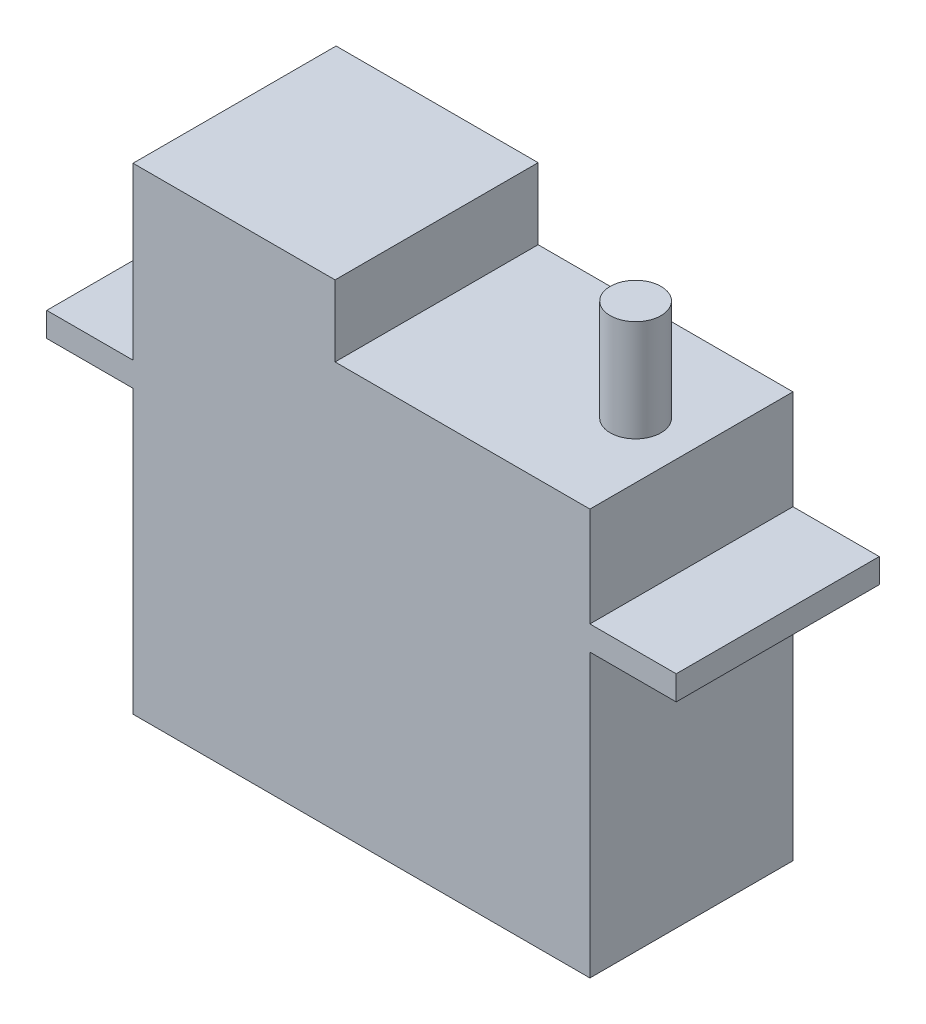
SolidWorks part; units mm, degrees
ref_plane "Plan de face" through (0, 0, 0) normal (0, 0, 1) x (1, 0, 0)
ref_plane "Plan de dessus" through (0, 0, 0) normal (0, 1, 0) x (1, 0, 0)
ref_plane "Plan de droite" through (0, 0, 0) normal (1, 0, 0) x (0, 0, -1)
sketch "Esquisse1" plane through (0, 0, 0) normal (0, 0, 1) x (1, 0, 0)
  line L0 (0, 0) -> (22.5, 0)
  line L1 (22.5, 0) -> (22.5, 15.1) construction
  line L2 (22.5, 15.1) -> (26.75, 15.1)
  line L3 (26.75, 15.1) -> (26.75, 13.9)
  line L4 (26.75, 13.9) -> (22.5, 13.9)
  line L5 (22.5, 13.9) -> (22.5, 20) construction
  line L6 (22.5, 20) -> (9.95, 20)
  line L7 (9.95, 20) -> (9.95, 23.5)
  line L8 (9.95, 23.5) -> (0, 23.5)
  line L9 (0, 23.5) -> (0, 13.9) construction
  line L10 (0, 13.9) -> (-4.25, 13.9)
  line L11 (-4.25, 13.9) -> (-4.25, 15.1)
  line L12 (-4.25, 15.1) -> (0, 15.1)
  line L13 (0, 15.1) -> (0, 0) construction
  line L14 (0, 23.5) -> (0, 15.1)
  line L15 (0, 13.9) -> (0, 0)
  line L16 (22.5, 13.9) -> (22.5, 0)
  line L17 (22.5, 20) -> (22.5, 15.1)
  dimension "D1" = 31
  dimension "D2" = 15.1
  dimension "D3" = 23.5
  dimension "D4" = 20
  dimension "D5" = 1.2
  dimension "D6" = 22.5
  dimension "D7" = 16.8
extrude "Boss.-Extru.1" add sketch "Esquisse1" along normal blind 5 and the other way blind 5 contours L6 L7 L8 L14 L12 L11 L10 L15 L0 L16 L4 L3 L2 L17
sketch "Esquisse3" plane through (0, 20, 0) normal (0, 1, 0) x (1, 0, 0)
  line L0 (26.75, 5) -> (26.75, -5) construction
  line L1 (9.95, 0) -> (19.75, 0) construction
  line L2 (9.95, 5) -> (9.95, -5) construction
  circle A0 centre (19.75, 0) radius 1.25
  dimension "D2" = 2.5
  dimension "D1" = 7
extrude "Boss.-Extru.2" add sketch "Esquisse3" along normal blind 5
